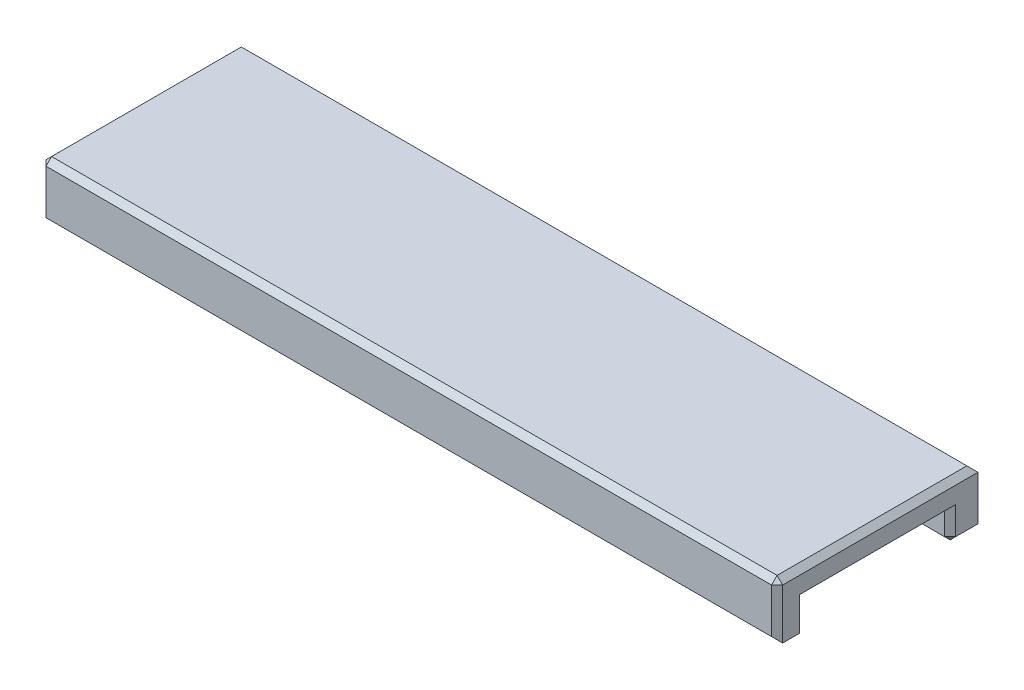
SolidWorks part; units mm, degrees
material "ABS"
ref_plane "Front Plane" through (0, 0, 0) normal (0, 0, 1) x (1, 0, 0)
ref_plane "Top Plane" through (0, 0, 0) normal (0, 1, 0) x (1, 0, 0)
ref_plane "Right Plane" through (0, 0, 0) normal (1, 0, 0) x (0, 0, -1)
sketch "Sketch1" plane through (0, 0, 0) normal (0, 1, 0) x (1, 0, 0)
  line L1 (-66, -18) -> (66, -18)
  line L2 (-66, -18) -> (-66, 18)
  line L3 (-66, 18) -> (66, 18)
  line L4 (66, -18) -> (66, 18)
  line L5 (-66, -18) -> (66, 18) construction
  line L6 (-66, 18) -> (66, -18) construction
  point P0 (0, 0)
  dimension "D1" = 132
  dimension "D2" = 36
extrude "Boss-Extrude1" add sketch "Sketch1" along normal mid plane 10
sketch "Sketch2" plane through (0, 0, 0) normal (1, 0, 0) x (0, 0, -1)
  line L0 (-13, 0) -> (13, 0)
  line L1 (13, 0) -> (13, -5)
  line L2 (-18, -5) -> (18, -5) construction
  line L3 (13, -5) -> (-13, -5)
  line L4 (-13, -5) -> (-13, 0)
  line L5 (-18, 5) -> (-18, -5) construction
  dimension "D1" = 5
extrude "Cut-Extrude1" cut sketch "Sketch2" against normal through all both and the other way through all
chamfer "Chamfer1" distance 1 angle 45 17 edges at (-66, -2.5, 13) (-66, -5, -15.5) (-66, 0, 0) (-66, -2.5, -13) (66, -5, -15.5) (66, -2.5, -13) (66, 0, 0) (66, -2.5, 13) (0, -5, 18) (66, 0, 18) (66, 5, 0) (0, 5, -18) (-66, 5, 0) (0, 5, 18) (-66, 0, 18) (0, -5, -13) (0, -5, 13)
